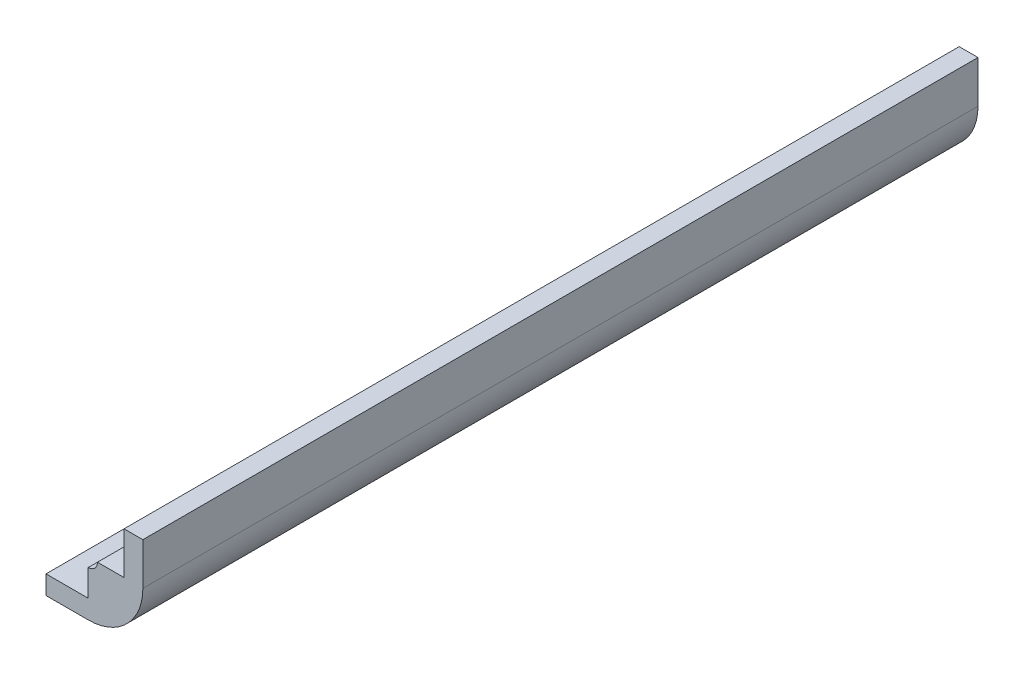
SolidWorks part; units mm, degrees
ref_plane "Front Plane" through (0, 0, 0) normal (0, 0, 1) x (1, 0, 0)
ref_plane "Top Plane" through (0, 0, 0) normal (0, 1, 0) x (1, 0, 0)
ref_plane "Right Plane" through (0, 0, 0) normal (1, 0, 0) x (0, 0, -1)
ref_axis "Axis1" through (0, 0, -88.99) along (0, 0, 1)
sketch "Sketch16" plane through (0, 0, 0) normal (0, 1, 0) x (1, 0, 0)
  line L0 (0, -43.9229) -> (0, 43.9229) construction
  point P2 (0, 0)
  dimension "D1" = 87.8459
sketch "Sketch2" plane through (0, 0, 0) normal (0, 0, 1) x (1, 0, 0)
  line L0 (-7.3025, -1.5) -> (-2.54, -1.5) construction
  line L1 (-7.3025, -1.5) -> (-7.3025, 1.5) construction
  line L2 (-2.54, -1.5) -> (-2.54, 1.5) construction
  line L3 (-7.3025, 1.5) -> (-2.54, 1.5) construction
  line L4 (-2.54, 0) -> (0, 0) construction
  line L5 (0, 0) -> (0, 2.54) construction
  line L6 (1.5, 2.54) -> (-1.5, 2.54) construction
  line L7 (1.5, 2.54) -> (1.5, 7.3025) construction
  line L8 (-1.5, 2.54) -> (-1.5, 7.3025) construction
  line L9 (1.5, 7.3025) -> (-1.5, 7.3025) construction
  point P7 (0, 2.54)
  point P16 (-1.5, 1.5)
  dimension "D1" = 3
  dimension "D2" = 4.7625
  dimension "D3" = 2.54
  dimension "D4" = 90
ref_plane "Plane1" through (0, 0, 0) normal (-1, 0, 0) x (0, 1, 0)
sketch "Sketch7" plane through (0, 0, 0) normal (0, 0, 1) x (1, 0, 0)
  line L0 (-7.3025, -1.5) -> (-2.54, -1.5)
  line L1 (-7.3025, -1.5) -> (-7.3025, -3.6212)
  line L2 (-2.54, -1.5) -> (-2.54, -3.6212)
  line L3 (-7.3025, -3.6212) -> (-2.54, -3.6212)
  dimension "D1" = 2.1212
extrude "Boss-Extrude2" add sketch "Sketch7" along normal mid plane 94.1959 separate body
sketch "Sketch8" plane through (0, 0, 0) normal (0, 0, 1) x (1, 0, 0)
  line L0 (1.5, 2.54) -> (1.5, 7.3025)
  line L1 (1.5, 2.54) -> (3.6212, 2.54)
  line L2 (1.5, 7.3025) -> (3.6212, 7.3025)
  line L3 (3.6212, 2.54) -> (3.6212, 7.3025)
  line L4 (-2.54, -3.6212) -> (-2.54, -1.5) construction
extrude "Boss-Extrude3" add sketch "Sketch8" along normal mid plane 94.1959
sketch "Sketch11" plane through (0, 0, 0) normal (0, 0, 1) x (1, 0, 0)
  line L1 (-2.54, -1.5) -> (-7.3025, -1.5)
  line L2 (-7.3025, -1.5) -> (-7.3025, -3.6212)
  line L8 (3.6212, 7.3025) -> (1.5, 7.3025)
  line L9 (1.5, 7.3025) -> (1.5, 2.54)
  line L13 (1.5, 2.54) -> (-1.5, 2.54)
  line L14 (-1.5, 2.54) -> (-1.5, 1.5) construction
  line L15 (-1.5, 1.5) -> (-2.54, 1.5) construction
  line L17 (-2.54, 1.5) -> (-2.54, -1.5)
  line L18 (3.6212, 7.3025) -> (3.6212, 2.54)
  line L19 (1.5, 2.54) -> (3.6212, 2.54) construction
  line L20 (-2.54, -3.6212) -> (-7.3025, -3.6212)
  arc A0 (-1.5, 2.54) -> (-2.54, 1.5) centre (-2.54, 2.54) cw
  arc A1 (3.6212, 2.54) -> (-2.54, -3.6212) centre (-2.54, 2.54) cw
extrude "Boss-Extrude4" add sketch "Sketch11" along normal mid plane 94.1959
ref_plane "Midplane" through (0, 0, 0) normal (0.7071, 0.7071, 0) x (0.7071, -0.7071, 0)
equation "\"plate_thickness\"= 3mm"
equation "\"D1@Sketch2\"=\"plate_thickness\""
equation "\"joiner_lip_width\"= .1875"
equation "\"D2@Sketch2\"=\"joiner_lip_width\""
equation "\"face_gap\"=0.1"
equation "\"D3@Sketch2\"=\"face_gap\""
equation "\"inside_angle\"= 90"
equation "\"joiner_thickness\"= 0.0835128"
equation "\"edge_length\"= 3.7085 - .25"
equation "\"Face1_TopLip\"= \"angle\" * 2"
equation "\"Face1_BottomLip\"= \"angle\" * 2"
equation "\"Face2_TopLip\"= 45deg"
equation "\"Face2_BottomLip\"= 45deg"
equation "\"D1@Sketch7\"=\"joiner_thickness\""
equation "\"D1@Boss-Extrude2\"=\"Extrude_to\""
equation "\"D1@Boss-Extrude3\"=\"Extrude_to\""
equation "\"D1@Boss-Extrude4\"=\"Extrude_to\""
equation "\"Extrude_to\"= \"edge_length\" + .25"
equation "\"D1@Sketch16\"=\"edge_length\""
equation "\"angle\"= atn ( 0.1 / ( ( 3.7085 - 3.0793 ) / 2 ) )"
equation "\"D2@Sketch5\"=\"Face2_TopLip\"/2"
equation "\"D1@Sketch5\"=\"Face2_BottomLip\"/2"
equation "\"D2@Sketch4\"=\"Face1_TopLip\"/2"
equation "\"D1@Sketch4\"=\"Face1_BottomLip\"/2"
equation "\"D1\" = \"edge_length\""
equation "\"D2@Sketch12\"=\"Face1_TopLip\"/2"
equation "\"D1@Sketch12\"=\"Face1_BottomLip\"/2"
